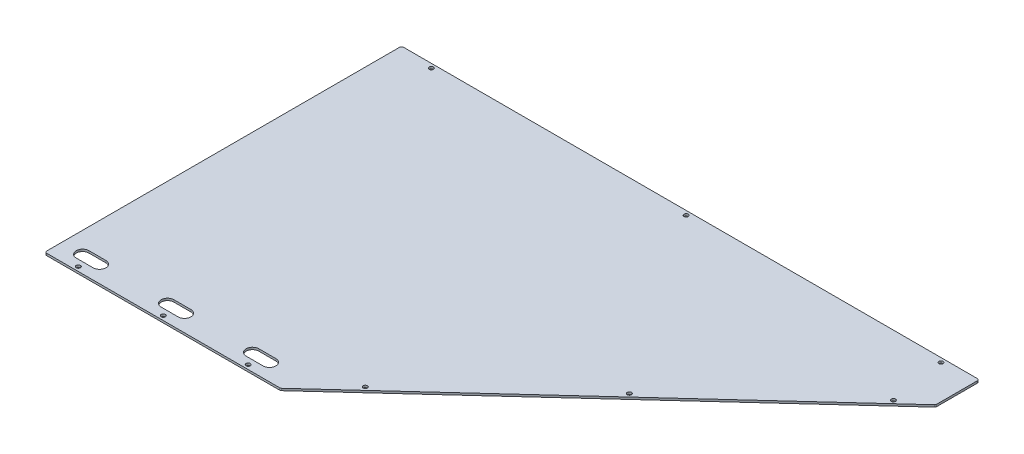
SolidWorks part; units mm, degrees
material "PE High Density"
ref_plane "Front Plane" through (0, 0, 0) normal (0, 0, 1) x (1, 0, 0)
ref_plane "Top Plane" through (0, 0, 0) normal (0, 1, 0) x (1, 0, 0)
ref_plane "Right Plane" through (0, 0, 0) normal (1, 0, 0) x (0, 0, -1)
sketch "Sketch1" plane through (0, 0, 0) normal (0, 1, 0) x (1, 0, 0)
  line L0 (0, 0) -> (352.425, 0)
  line L1 (352.425, 0) -> (863.6, 468.4056)
  line L2 (863.6, 533.4) -> (0, 533.4)
  line L7 (0, 533.4) -> (0, 0)
  line L8 (863.6, 533.4) -> (863.6, 468.4056)
  point P3 (0, 527.6007)
  dimension "D4" = 863.6
  dimension "D1" = 352.425
  dimension "D2" = 533.4
  dimension "D3" = 137.5
extrude "Boss-Extrude1" add sketch "Sketch1" along normal blind 3.175
fillet "Fillet1" radius 3.175 5 edges at (0, 1.5875, 0) (863.6, 1.5875, -533.4) (863.6, 1.5875, -468.4056) (352.425, 1.5875, 0) (0, 1.5875, -533.4)
sketch "Sketch2" plane through (0, 3.175, 0) normal (0, 1, 0) x (1, 0, 0)
  line L0 (43.8327, 6.35) -> (297.8327, 6.35) construction
  line L1 (414.0534, 65.0848) -> (826.0439, 442.6046) construction
  line L2 (353.3353, 0.8341) -> (862.57, 467.4618) construction
  line L3 (3.175, 0) -> (351.1903, 0) construction
  line L4 (603.6627, 238.8297) -> (607.9527, 234.148) construction
  line L5 (50.8, 527.05) -> (812.8, 527.05) construction
  line L6 (860.425, 533.4) -> (3.175, 533.4) construction
  point P0 (43.8327, 6.35)
  point P1 (170.8327, 6.35)
  point P2 (297.8327, 6.35)
  point P3 (414.0534, 65.0848)
  point P4 (620.0486, 253.8447)
  point P5 (826.0439, 442.6046)
  point P10 (607.9527, 234.148)
  point P16 (177.1827, 0)
  point P20 (431.8, 533.4)
  point P21 (431.8, 527.05)
  dimension "D1" = 6.35
  dimension "D2" = 6.35
  dimension "D3" = 254
  dimension "D4" = 558.8
  dimension "D5" = 6.35
  dimension "D6" = 22.225
  dimension "D7" = 6.35
  dimension "D8" = 762
hole_wizard "1/4 (0.25) Diameter Hole1" positions "Sketch3" profile "Sketch4" hole size "1/4" standard "ANSI Inch" end condition through all
sketch "Sketch3" plane through (0, 3.175, 0) normal (0, 1, 0) x (1, 0, 0)
  point P0 (43.8327, 6.35)
  point P3 (170.8327, 6.35)
  point P6 (297.8327, 6.35)
  point P9 (414.0534, 65.0848)
  point P12 (620.0486, 253.8447)
  point P15 (826.0439, 442.6046)
  point P19 (50.8, 527.05)
  point P22 (431.8, 527.05)
  point P25 (812.8, 527.05)
sketch "Sketch4" plane through (43.8327, 3.175, -6.35) normal (1, 0, 0) x (0, 0, 1)
  line L0 (0, 0) -> (0, 3.175)
  line L1 (0, 3.175) -> (3.175, 3.175)
  line L2 (3.175, 3.175) -> (3.175, 0)
  line L5 (3.175, 0) -> (0, 0)
  line L11 (0, -6.35) -> (0, 107.95) construction
  dimension "Thru Hole Dia." = 6.35
  dimension "Thru Hole Depth" = 3.175
sketch "Sketch5" plane through (0, 3.175, 0) normal (0, 1, 0) x (1, 0, 0)
  line L0 (31.1327, 25.4) -> (56.5327, 25.4) construction
  line L1 (31.1327, 34.925) -> (56.5327, 34.925)
  line L2 (31.1327, 15.875) -> (56.5327, 15.875)
  line L3 (158.1327, 25.4) -> (183.5327, 25.4) construction
  line L4 (158.1327, 34.925) -> (183.5327, 34.925)
  line L5 (158.1327, 15.875) -> (183.5327, 15.875)
  line L6 (285.1327, 25.4) -> (310.5327, 25.4) construction
  line L7 (285.1327, 34.925) -> (310.5327, 34.925)
  line L8 (285.1327, 15.875) -> (310.5327, 15.875)
  circle A0 centre (297.8327, 6.35) radius 3.175 construction
  circle A1 centre (170.8327, 6.35) radius 3.175 construction
  circle A2 centre (43.8327, 6.35) radius 3.175 construction
  circle A3 centre (297.8327, 6.35) radius 3.175
  circle A4 centre (170.8327, 6.35) radius 3.175
  circle A5 centre (43.8327, 6.35) radius 3.175
  arc A6 (31.1327, 34.925) -> (31.1327, 15.875) centre (31.1327, 25.4) ccw
  arc A7 (56.5327, 15.875) -> (56.5327, 34.925) centre (56.5327, 25.4) ccw
  arc A8 (158.1327, 34.925) -> (158.1327, 15.875) centre (158.1327, 25.4) ccw
  arc A9 (183.5327, 15.875) -> (183.5327, 34.925) centre (183.5327, 25.4) ccw
  arc A10 (285.1327, 34.925) -> (285.1327, 15.875) centre (285.1327, 25.4) ccw
  arc A11 (310.5327, 15.875) -> (310.5327, 34.925) centre (310.5327, 25.4) ccw
  point P11 (43.8327, 25.4)
  point P17 (170.8327, 25.4)
  point P24 (297.8327, 25.4)
  point P30 (0, 0)
  point P31 (0, 0)
  point P32 (0, 0)
  dimension "D1" = 9.525
  dimension "D2" = 19.05
  dimension "D3" = 25.4
extrude "Cut-Extrude1" cut sketch "Sketch5" against normal through all
